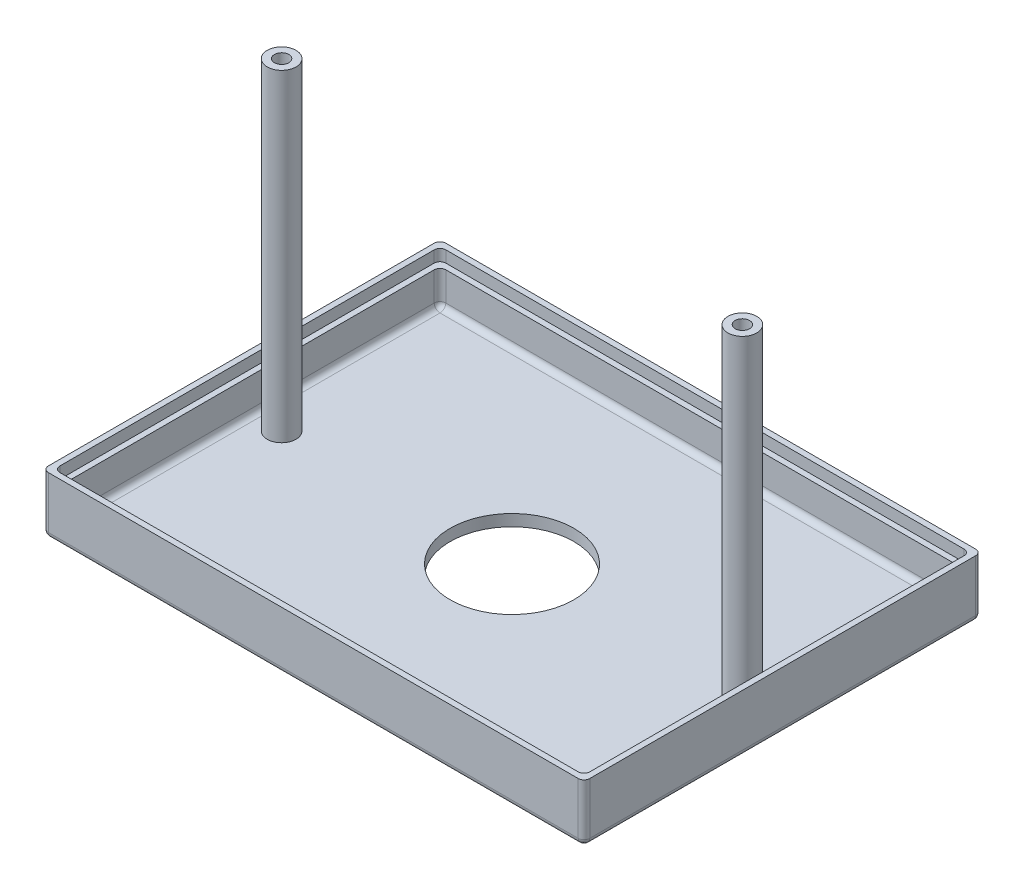
SolidWorks part; units mm, degrees
ref_plane "Front Plane" through (0, 0, 0) normal (0, 0, 1) x (1, 0, 0)
ref_plane "Top Plane" through (0, 0, 0) normal (0, 1, 0) x (1, 0, 0)
ref_plane "Right Plane" through (0, 0, 0) normal (1, 0, 0) x (0, 0, -1)
sketch "Sketch1" plane through (0, 0, 0) normal (0, 1, 0) x (1, 0, 0)
  line L1 (45, 32.5) -> (-45, 32.5)
  line L2 (45, 32.5) -> (45, -32.5)
  line L3 (45, -32.5) -> (-45, -32.5)
  line L4 (-45, 32.5) -> (-45, -32.5)
  line L5 (45, 32.5) -> (-45, -32.5) construction
  line L6 (45, -32.5) -> (-45, 32.5) construction
  point P0 (0, 0)
  dimension "D1" = 90
  dimension "D2" = 65
extrude "Boss-Extrude1" add sketch "Sketch1" along normal blind 8
shell "Shell1" thickness 2 removed face at (0, 8, 0) outward yes
sketch "Sketch2" plane through (0, 0, 0) normal (0, 1, 0) x (1, 0, 0)
  line L0 (-45, 32.5) -> (-45, -32.5) construction
  circle A0 centre (-40, 0) radius 2.5
  circle A1 centre (40, 0) radius 2.5
  dimension "D2" = 5
  dimension "D1" = 5
sketch "Sketch3" plane through (0, 8, 0) normal (0, 1, 0) x (1, 0, 0)
  line L0 (45, 32.5) -> (-45, 32.5) construction
  line L1 (45, -32.5) -> (45, 32.5) construction
  line L2 (-45, -32.5) -> (45, -32.5) construction
  line L3 (-45, 32.5) -> (-45, -32.5) construction
  line L4 (45, 32.5) -> (-45, 32.5)
  line L5 (45, -32.5) -> (45, 32.5)
  line L6 (-45, -32.5) -> (45, -32.5)
  line L7 (-45, 32.5) -> (-45, -32.5)
  line L8 (46, 33.5) -> (-46, 33.5)
  line L9 (-46, 33.5) -> (-46, -33.5)
  line L10 (-46, -33.5) -> (46, -33.5)
  line L11 (46, -33.5) -> (46, 33.5)
  dimension "D1" = 1
extrude "Cut-Extrude1" cut sketch "Sketch3" against normal blind 2
fillet "Fillet2" radius 1 4 edges at (46, 7, 33.5) (46, 7, -33.5) (-46, 7, 33.5) (-46, 7, -33.5)
fillet "Fillet3" radius 1 4 edges at (0, 0, -32.5) (45, 0, 0) (0, 0, 32.5) (-45, 0, 0)
fillet "Fillet4" radius 1 8 edges at (44.7071, 0.2929, 32.2071) (44.7071, 0.2929, -32.2071) (-44.7071, 0.2929, -32.2071) (-44.7071, 0.2929, 32.2071) (45, 3.5, 32.5) (45, 3.5, -32.5) (-45, 3.5, -32.5) (-45, 3.5, 32.5)
extrude "Boss-Extrude2" add sketch "Sketch2" along normal blind 56 contours A0 | A1
sketch "Sketch4" plane through (0, 56, 0) normal (0, 1, 0) x (1, 0, 0)
  circle A0 centre (40, 0) radius 1.25
  circle A1 centre (-40, 0) radius 1.25
  dimension "D1" = 2.5
  dimension "D2" = 2.5
extrude "Cut-Extrude2" cut sketch "Sketch4" against normal blind 10
fillet "Fillet5" radius 1 2 edges at (-40, 46, 1.25) (40, 46, 1.25)
sketch "Sketch5" plane through (0, -2, 0) normal (0, -1, 0) x (-1, 0, 0)
  circle A0 centre (0, 0) radius 10.75
  dimension "D1" = 21.5
extrude "Cut-Extrude3" cut sketch "Sketch5" against normal blind 10
sketch "Sketch6" plane through (0, -2, 0) normal (0, -1, 0) x (-1, 0, 0)
  circle A0 centre (-41.2675, -28.6721) radius 1.5
  dimension "D1" = 3
extrude "Cut-Extrude4" cut sketch "Sketch6" against normal blind 10
fillet "Fillet6" radius 1 8 edges at (0, -2, 34.5) (-47, 3, 34.5) (-47, -2, 0) (-47, 3, -34.5) (47, 3, -34.5) (0, -2, -34.5) (47, -2, 0) (47, 3, 34.5)
